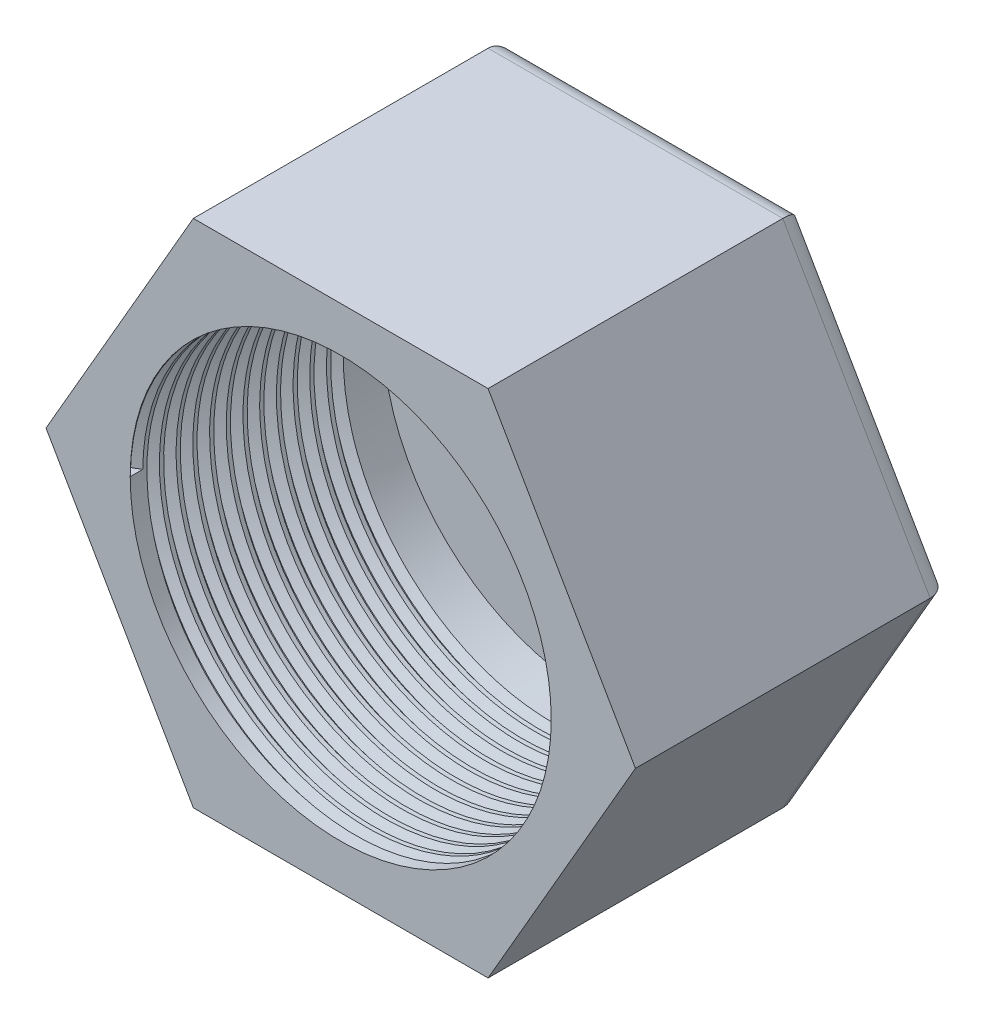
SolidWorks part; units mm, degrees
ref_plane "Front Plane" through (0, 0, 0) normal (0, 0, 1) x (1, 0, 0)
ref_plane "Top Plane" through (0, 0, 0) normal (0, 1, 0) x (1, 0, 0)
ref_plane "Right Plane" through (0, 0, 0) normal (1, 0, 0) x (0, 0, -1)
sketch "Sketch2" plane through (0, 0, 0) normal (0, 0, 1) x (1, 0, 0)
  line L2 (-29.9933, 3.7044) -> (-36.9933, 15.8288)
  line L3 (-36.9933, 15.8288) -> (-50.9933, 15.8288)
  line L4 (-50.9933, 15.8288) -> (-57.9933, 3.7044)
  line L5 (-57.9933, 3.7044) -> (-50.9933, -8.4199)
  line L6 (-50.9933, -8.4199) -> (-36.9933, -8.4199)
  line L7 (-36.9933, -8.4199) -> (-29.9933, 3.7044)
  circle A0 centre (-43.9933, 3.7044) radius 12.1244 construction
extrude "Boss-Extrude1" add sketch "Sketch2" along normal blind 15
sketch "Sketch4" plane through (0, 0, 15) normal (0, 0, 1) x (1, 0, 0)
  circle A1 centre (-43.9933, 3.7044) radius 10
extrude "Cut-Extrude2" cut sketch "Sketch4" against normal blind 12
sketch "Sketch5" plane through (0, 0, 0) normal (0, 0, -1) x (-1, 0, 0)
  circle A1 centre (43.9933, 3.7044) radius 4
extrude "Boss-Extrude2" add sketch "Sketch5" along normal blind 2
thread "Thread2" pitch 0.7937 method cut profile "Thread Profile2" start angle 0, offset 0, length 10, pitch 0.7937, diameter 20
ref_plane "Plane2" through (-53.9933, 3.7044, 15) normal (0, -1, 0) x (-1, 0, 0)
sketch "Thread Profile2" plane through (-53.9933, 3.7044, 15) normal (0, -1, 0) x (-1, 0, 0)
  line L0 (0, 0) -> (0, 0.7937) construction
  line L1 (0, 0) -> (0.4296, 0.248)
  line L2 (0.4296, 0.248) -> (0.4296, 0.3473)
  line L3 (0.4296, 0.3473) -> (0, 0.5953)
  line L4 (0.4296, 0.2977) -> (0, 0.2977) construction
  line L11 (0, 0) -> (0, 0.5953)
  point P2 (0, 0)
  dimension "Pitch" = 0.7937
  dimension "Profile_Angle" = 60
  dimension "Profile_Land" = 0.0992
  dimension "Profile_Height" = 0.4296
fillet "Fillet1" radius 1 6 edges at (-43.9933, -8.4199, 0) (-33.4933, -2.3578, 0) (-33.4933, 9.7666, 0) (-43.9933, 15.8288, 0) (-54.4933, 9.7666, 0) (-54.4933, -2.3578, 0)
